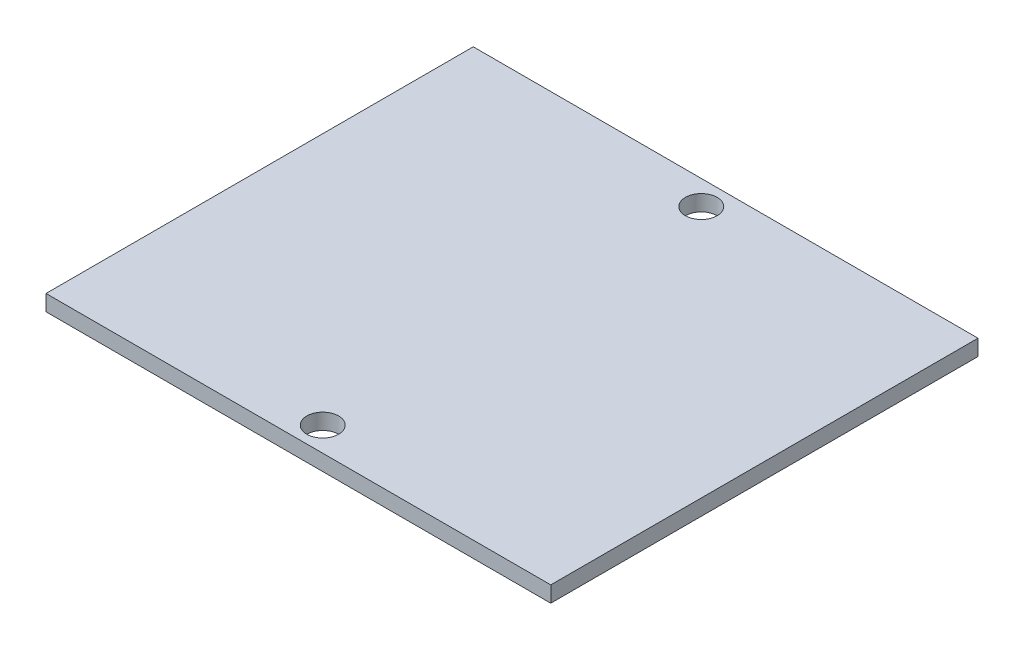
SolidWorks part; units mm, degrees
ref_plane "Front Plane" through (0, 0, 0) normal (0, 0, 1) x (1, 0, 0)
ref_plane "Top Plane" through (0, 0, 0) normal (0, 1, 0) x (1, 0, 0)
ref_plane "Right Plane" through (0, 0, 0) normal (1, 0, 0) x (0, 0, -1)
sketch "Sketch1" plane through (0, 0, 0) normal (0, 1, 0) x (1, 0, 0)
  line L1 (0, 0) -> (50.8, 0)
  line L2 (0, 0) -> (0, 43)
  line L3 (0, 43) -> (50.8, 43)
  line L4 (50.8, 0) -> (50.8, 43)
  circle A2 centre (25.4, 40.55) radius 1.6
  circle A3 centre (25.4, 2.45) radius 1.6
  point P7 (0, 0)
  point P8 (16.6133, 36.5931)
  point P9 (0, 0)
  point P12 (25.4, 43)
  point P13 (25.4, 2.2995)
  point P15 (25.0197, 39.4549)
  point P16 (24.7334, 37.8083)
  dimension "D3" = 2.45
  dimension "D2" = 38.1
  dimension "D4" = 3.2
  dimension "D1" = 43
  dimension "50.8" = 50.8
extrude "Boss-Extrude1" add sketch "Sketch1" along normal blind 1.6002
